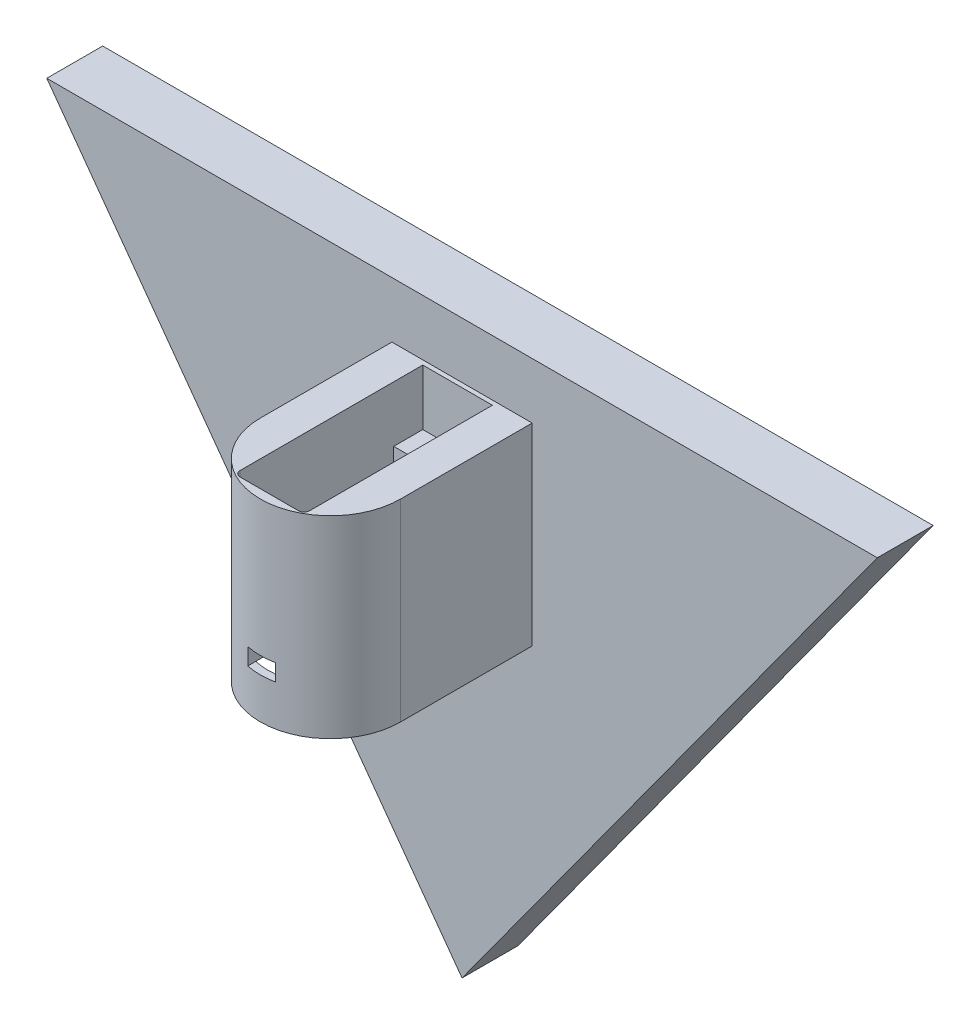
SolidWorks part; units mm, degrees
ref_plane "Front Plane" through (0, 0, 0) normal (0, 0, 1) x (1, 0, 0)
ref_plane "Top Plane" through (0, 0, 0) normal (0, 1, 0) x (1, 0, 0)
ref_plane "Right Plane" through (0, 0, 0) normal (1, 0, 0) x (0, 0, -1)
sketch "Sketch4" plane through (0, 0, 0) normal (0, 0, 1) x (1, 0, 0)
  line L0 (55, 0) -> (-55, 0) construction
  line L1 (-6.23, -9.975) -> (6.23, -9.975)
  line L2 (-6.23, -9.975) -> (-6.23, 7.275)
  line L3 (-6.23, 7.275) -> (6.23, 7.275)
  line L4 (6.23, -9.975) -> (6.23, 7.275)
  point P4 (0, 7.275)
  dimension "D1" = 12.46
  dimension "D2" = 17.25
  dimension "D3" = 9.975
extrude "Boss-Extrude3" add sketch "Sketch4" along normal blind 6
sketch "Sketch8" plane through (0, -9.975, 0) normal (0, -1, 0) x (-1, 0, 0)
  circle A0 centre (0, -23.55) radius 12.5468
  circle A1 centre (0, -23.55) radius 11.15
  dimension "D1" = 22.3
  dimension "D2" = 23.55
extrude "Boss-Extrude6" add sketch "Sketch8" along normal blind 7.3 and the other way up to surface (17.25 mm away) other way up to face at (0, 7.275, 3)
sketch "Sketch5" plane through (0, 7.275, 0) normal (0, 1, 0) x (1, 0, 0)
  line L8 (12.5468, -23.55) -> (12.5468, 0)
  line L9 (12.5468, 0) -> (6.23, 0)
  line L10 (-12.5468, -23.55) -> (-12.5468, 0)
  line L11 (-12.5468, 0) -> (-6.23, 0)
  line L12 (-6.23, 0) -> (-6.23, -29.7)
  line L14 (6.23, -29.7) -> (6.23, 0)
  line L15 (-6.23, -29.7) -> (6.23, -29.7)
  line L16 (6.23, -6) -> (-6.23, -6) construction
  circle A0 centre (0, -23.55) radius 12.5468 construction
  arc A1 (-12.5468, -23.55) -> (12.5468, -23.55) centre (0, -23.55) ccw
  dimension "D1" = 23.7
  dimension "D2" = 23.55
extrude "Boss-Extrude4" add sketch "Sketch5" against normal up to surface (17.25 mm away) up to face at (0, -9.975, 3)
sketch "Sketch6" plane through (0, 7.275, 0) normal (0, 1, 0) x (1, 0, 0)
  line L0 (6.23, -6) -> (-6.23, -6) construction
  line L3 (6.23, -29.7) -> (-6.23, -29.7) construction
  circle A0 centre (0, -3.5) radius 2
  circle A1 centre (0, -32.2) radius 2
  dimension "D1" = 4
  dimension "D3" = 4
  dimension "D2" = 2.5
  dimension "D4" = 2.5
extrude "Cut-Extrude1" cut sketch "Sketch6" against normal blind 5
chamfer "Chamfer1" distance 0.5 angle 60 2 edges at (0, 7.275, 5.5) (0, 7.275, 34.2) first distance on face at (0, 7.275, 5.5)
sketch "Sketch10" plane through (0, 7.275, 0) normal (0, 1, 0) x (1, 0, 0)
  line L1 (-6.23, -6) -> (6.23, -6)
  line L2 (-6.23, -6) -> (-6.23, -29.7)
  line L3 (-6.23, -29.7) -> (6.23, -29.7)
  line L4 (6.23, -6) -> (6.23, -29.7)
extrude "Cut-Extrude3" cut sketch "Sketch10" against normal up to surface (17.25 mm away) up to face at (0, -9.975, 10.3399)
ref_plane "Plane1" through (0, 0, 36.0968) normal (0, 0, 1) x (1, 0, 0)
sketch "Sketch11" plane through (0, 0, 36.0968) normal (0, 0, 1) x (1, 0, 0)
  line L0 (-11.15, -9.975) -> (11.15, -9.975) construction
  line L1 (-2.5, -6.975) -> (2.5, -6.975)
  line L2 (-2.5, -6.975) -> (-2.5, -9.975)
  line L3 (-2.5, -9.975) -> (2.5, -9.975)
  line L4 (2.5, -6.975) -> (2.5, -9.975)
  point P4 (0, -6.975)
  dimension "D1" = 0
  dimension "D2" = 5
  dimension "D3" = 3
extrude "Cut-Extrude4" cut sketch "Sketch11" against normal up to next
sketch "Sketch13" plane through (0, -17.275, 0) normal (0, -1, 0) x (1, 0, 0)
  line L0 (-12.5468, 23.55) -> (-12.5468, 0)
  line L1 (-12.5468, 0) -> (12.5468, 0)
  line L2 (12.5468, 0) -> (12.5468, 23.55)
  arc A0 (-12.5468, 23.55) -> (12.5468, 23.55) centre (0, 23.55) ccw
  point P3 (0, 0)
extrude "Boss-Extrude7" add sketch "Sketch13" against normal up to surface (7.3 mm away) up to face at (0, -9.975, 10.3399)
sketch "Sketch15" plane through (0, 7.275, 0) normal (0, 1, 0) x (1, 0, 0)
  line L0 (-12.5468, 0) -> (12.5468, 0)
  line L1 (12.5468, 0) -> (12.5468, -23.55)
  line L2 (-12.5468, 0) -> (-12.5468, -23.55)
  line L3 (6.23, -6) -> (6.23, -29.7) construction
  line L4 (-6.23, -0.8) -> (6.23, -0.8)
  line L5 (-6.23, -0.8) -> (-6.23, -33.5)
  line L6 (-5.23, -34.5) -> (5.23, -34.5)
  line L7 (6.23, -0.8) -> (6.23, -33.5)
  arc A0 (-12.5468, -23.55) -> (12.5468, -23.55) centre (0, -23.55) ccw
  circle A1 centre (0, -3.5) radius 2 construction
  arc A2 (5.23, -34.5) -> (6.23, -33.5) centre (5.23, -33.5) ccw
  arc A3 (-6.23, -33.5) -> (-5.23, -34.5) centre (-5.23, -33.5) ccw
  point P15 (0, -0.8)
  dimension "D1" = 0.8
  dimension "D3" = 1
  dimension "D2" = 2.7
  dimension "D4" = 0
  dimension "D5" = 34.5
extrude "Boss-Extrude9" add sketch "Sketch15" along normal blind 10
sketch "Sketch1" plane through (0, 0, 0) normal (0, 0, 1) x (1, 0, 0)
  line L0 (0, -75) -> (74.3071, 27.275)
  line L1 (74.3071, 27.275) -> (-74.3071, 27.275)
  line L2 (-74.3071, 27.275) -> (0, -75)
  line L3 (6.23, 17.275) -> (-6.23, 17.275) construction
  line L4 (13.8015, 0) -> (-13.8015, 0) construction
  point P6 (-4.6467, -53.5054)
  point P7 (0, 0)
  point P10 (0, 27.275)
  dimension "D2" = 10
  dimension "D1" = 72
  dimension "D3" = 75
extrude "Offset R" add sketch "Sketch1" against normal blind 10 contours L2 L0 L1
